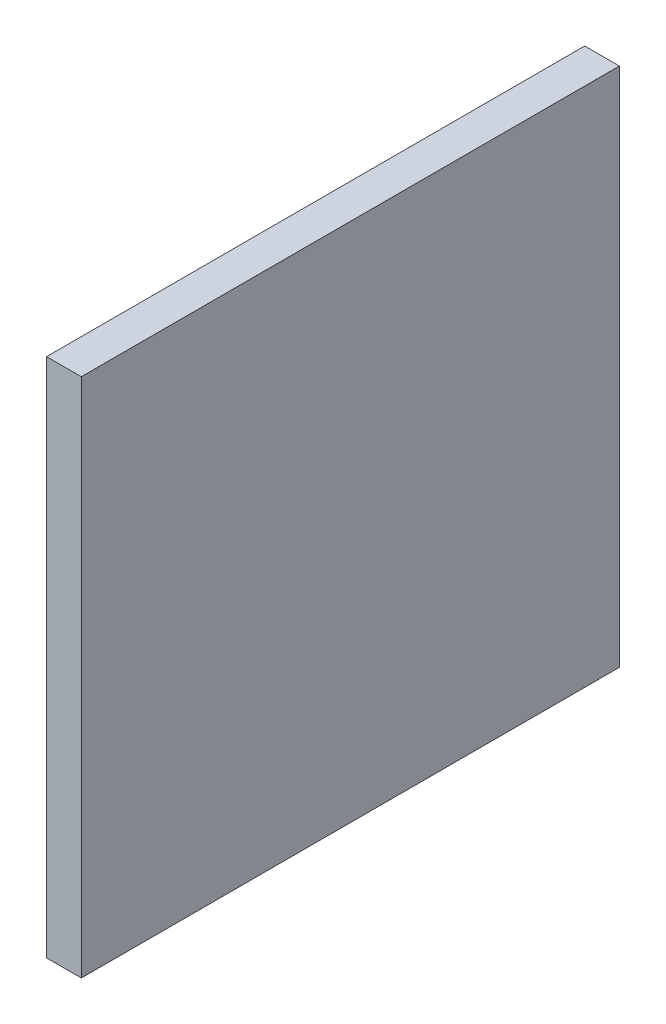
SolidWorks part; units mm, degrees
ref_plane "Front Plane" through (0, 0, 0) normal (0, 0, 1) x (1, 0, 0)
ref_plane "Top Plane" through (0, 0, 0) normal (0, 1, 0) x (1, 0, 0)
ref_plane "Right Plane" through (0, 0, 0) normal (1, 0, 0) x (0, 0, -1)
sketch "Sketch1" plane through (0, 0, 0) normal (0, 0, 1) x (1, 0, 0)
  line L0 (0, 0) -> (0, -150) construction
  line L1 (0, -150) -> (150, -150) construction
  line L2 (150, -150) -> (150, 0) construction
  line L3 (150, -150) -> (150, 0)
  line L4 (150, 0) -> (160, 0)
  line L5 (160, 0) -> (160, -150)
  line L6 (160, -150) -> (150, -150)
  circle A0 centre (0, 0) radius 150 construction
  dimension "D1" = 300
  dimension "D2" = 10
extrude "Boss-Extrude1" add sketch "Sketch1" along normal blind 155
